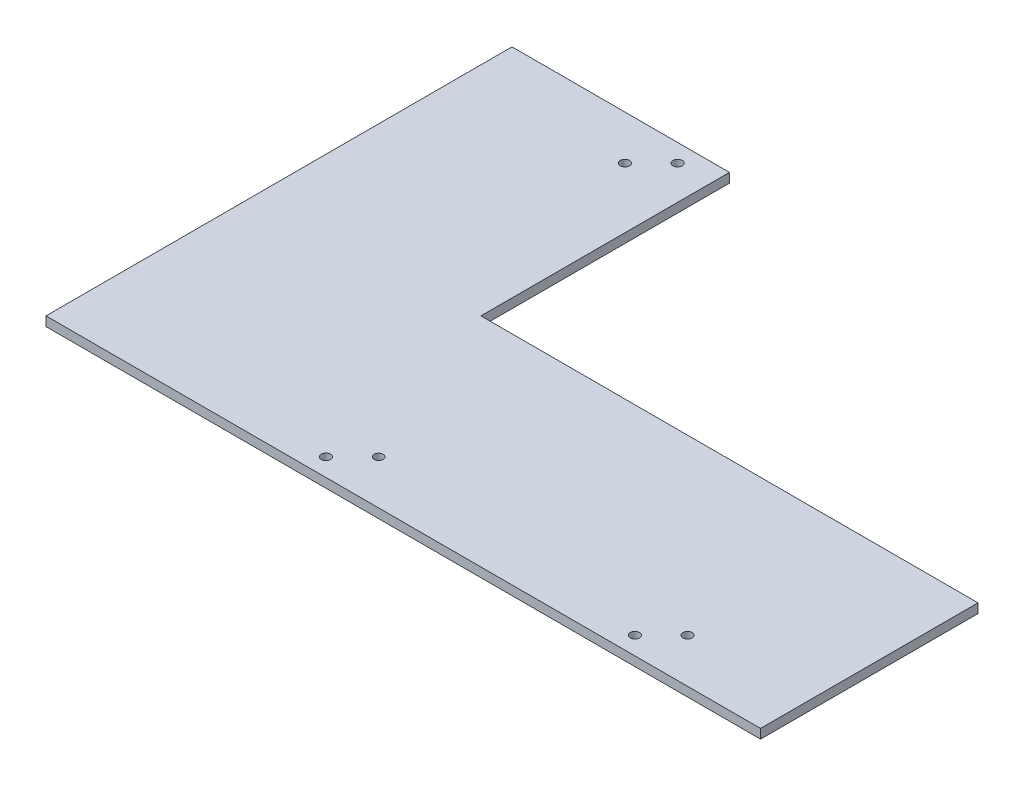
SolidWorks part; units mm, degrees
ref_plane "Front Plane" through (0, 0, 0) normal (0, 0, 1) x (1, 0, 0)
ref_plane "Top Plane" through (0, 0, 0) normal (0, 1, 0) x (1, 0, 0)
ref_plane "Right Plane" through (0, 0, 0) normal (1, 0, 0) x (0, 0, -1)
sketch "Sketch1" plane through (0, 0, 0) normal (0, 1, 0) x (1, 0, 0)
  line L0 (-115, -35) -> (115, -35)
  line L2 (-115, -35) -> (-115, 35)
  line L4 (115, -35) -> (115, 35)
  line L5 (-115, -35) -> (115, 35) construction
  line L6 (-115, 35) -> (115, -35) construction
  line L15 (-45, 35) -> (115, 35)
  line L17 (-115, 35) -> (-115, 115)
  line L18 (-115, 115) -> (-45, 115)
  line L19 (-45, 35) -> (-45, 115)
  circle A0 centre (-30.6532, -29.2426) radius 1.5
  circle A1 centre (-22.168, -20.7574) radius 1.4446
  circle A2 centre (68.7949, -29.2426) radius 1.5
  circle A3 centre (77.2802, -20.7574) radius 1.5
  circle A4 centre (-64.4104, 100.7574) radius 1.5
  circle A5 centre (-55.9252, 109.2426) radius 1.5
  point P0 (0, 0)
  dimension "D1" = 230
  dimension "D2" = 70
  dimension "D3" = 70
  dimension "D4" = 150
extrude "Boss-Extrude1" add sketch "Sketch1" along normal blind 3
